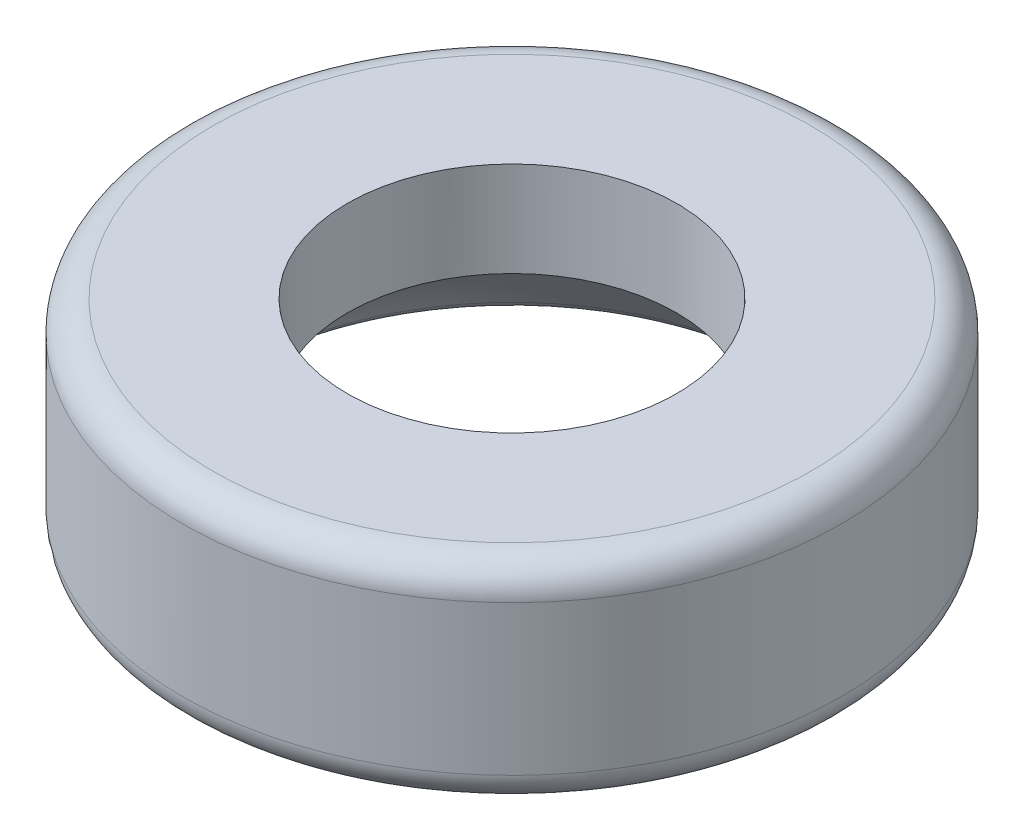
SolidWorks part; units mm, degrees
ref_plane "Front" through (0, 0, 0) normal (0, 0, 1) x (1, 0, 0)
ref_plane "Top" through (0, 0, 0) normal (0, 1, 0) x (1, 0, 0)
ref_plane "Right" through (0, 0, 0) normal (1, 0, 0) x (0, 0, -1)
sketch "Sketch1" plane through (0, 0, 0) normal (0, 0, 1) x (1, 0, 0)
  line L0 (-74.224, 0) -> (3636.9745, 0) construction
  line L1 (0, -74.224) -> (0, 3636.9745) construction
  line L2 (4.1275, 0) -> (4.1275, 4.7625)
  line L3 (4.1275, 4.7625) -> (0, 4.7625)
  line L4 (0, 4.7625) -> (0, 4.1275)
  arc A0 (0, 4.1275) -> (4.1275, 0) centre (0, 0) cw
  dimension "D4" = 4.1275
  dimension "D1" = 4.7625
  dimension "D2" = 4.1275
  dimension "D3" = 0.635
revolve "Revolve1" add sketch "Sketch1" angle 360 about L1
fillet "Fillet1" radius 0.381 2 edges at (4.1275, 0, 0) (4.1275, 4.7625, 0)
sketch "Sketch2" plane through (0, 4.7625, 0) normal (0, 1, 0) x (1, 0, 0)
  circle A0 centre (0, 0) radius 2.0638
  dimension "D1" = 4.1275
extrude "Cut-Extrude1" cut sketch "Sketch2" against normal through all
